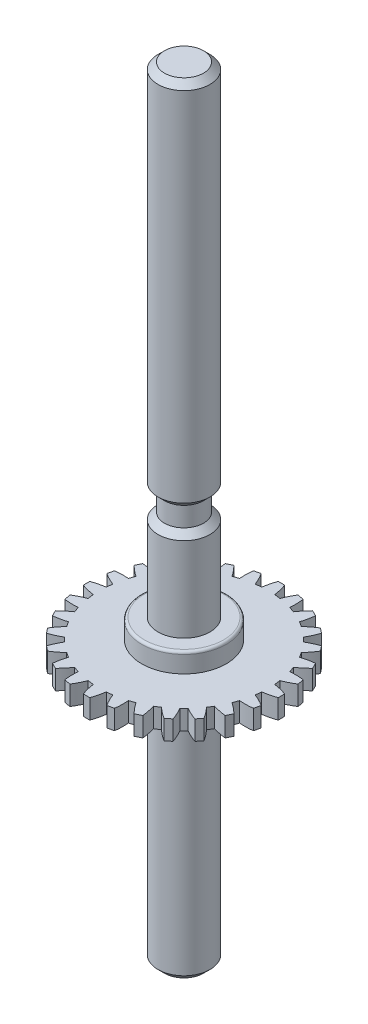
SolidWorks part; units mm, degrees
ref_plane "前视基准面" through (0, 0, 0) normal (0, 0, 1) x (1, 0, 0)
ref_plane "上视基准面" through (0, 0, 0) normal (0, 1, 0) x (1, 0, 0)
ref_plane "右视基准面" through (0, 0, 0) normal (1, 0, 0) x (0, 0, -1)
sketch "草图1" plane through (0, 0, 0) normal (0, 1, 0) x (1, 0, 0)
  circle A0 centre (0, 0) radius 6.5
extrude "凸台-拉伸1" add sketch "草图1" along normal blind 1.5
sketch "草图2" plane through (0, 1.5, 0) normal (0, 1, 0) x (-1, 0, 0)
  circle A0 centre (0, 0) radius 3.25
extrude "凸台-拉伸2" add sketch "草图2" along normal blind 1.5
sketch "草图3" plane through (0, 3, 0) normal (0, 1, 0) x (-1, 0, 0)
  circle A0 centre (0, 0) radius 2
extrude "凸台-拉伸3" add sketch "草图3" along normal blind 37
sketch "草图4" plane through (0, 1.5, 0) normal (0, 1, 0) x (-1, 0, 0)
  circle A0 centre (0, 0) radius 2
  circle A1 centre (0, 0) radius 1.5
extrude "切除-拉伸1" cut sketch "草图4" along normal blind 1.5 from offset 8.5
chamfer "倒角1" distance 0.5 angle 45 2 edges at (0, 10, 2) (0, 11.5, 2)
fillet "圆角1" radius 0.2 1 edges at (0, 3, 3.25)
sketch "草图9" plane through (0, 0, 0) normal (0, -1, 0) x (1, 0, 0)
  line L0 (1.4252, 7.3676) -> (1.9126, 7.2563)
  line L1 (-0.25, 7.5) -> (0.25, 7.5)
  line L2 (3.0289, 6.8657) -> (3.4794, 6.6488)
  line L3 (4.4807, 6.0196) -> (4.8716, 5.7079)
  line L4 (5.7079, 4.8716) -> (6.0196, 4.4807)
  line L5 (6.6488, 3.4794) -> (6.8657, 3.0289)
  line L6 (7.2563, 1.9126) -> (7.3676, 1.4252)
  line L7 (7.5, 0.25) -> (7.5, -0.25)
  line L8 (7.3676, -1.4252) -> (7.2563, -1.9126)
  line L9 (6.8657, -3.0289) -> (6.6488, -3.4794)
  line L10 (6.0196, -4.4807) -> (5.7079, -4.8716)
  line L11 (4.8716, -5.7079) -> (4.4807, -6.0196)
  line L12 (3.4794, -6.6488) -> (3.0289, -6.8657)
  line L13 (1.9126, -7.2563) -> (1.4252, -7.3676)
  line L14 (0.25, -7.5) -> (-0.25, -7.5)
  line L15 (-1.4252, -7.3676) -> (-1.9126, -7.2563)
  line L16 (-3.0289, -6.8657) -> (-3.4794, -6.6488)
  line L17 (-4.4807, -6.0196) -> (-4.8716, -5.7079)
  line L18 (-5.7079, -4.8716) -> (-6.0196, -4.4807)
  line L19 (-6.6488, -3.4794) -> (-6.8657, -3.0289)
  line L20 (-7.2563, -1.9126) -> (-7.3676, -1.4252)
  line L21 (-7.5, -0.25) -> (-7.5, 0.25)
  line L22 (-7.3676, 1.4252) -> (-7.2563, 1.9126)
  line L23 (-6.8657, 3.0289) -> (-6.6488, 3.4794)
  line L24 (-6.0196, 4.4807) -> (-5.7079, 4.8716)
  line L25 (-4.8716, 5.7079) -> (-4.4807, 6.0196)
  line L26 (-3.4794, 6.6488) -> (-3.0289, 6.8657)
  line L27 (-1.9126, 7.2563) -> (-1.4252, 7.3676)
  arc A0 (0.5, 6.4807) -> (-0.5, 6.4807) centre (0, 0) ccw
  arc A1 (0.5, 6.4807) -> (0.25, 7.5) centre (-4.6435, 5.7595) ccw
  arc A2 (-0.5, 6.4807) -> (-0.25, 7.5) centre (4.6435, 5.7595) cw
  arc A3 (1.9296, 6.207) -> (0.9546, 6.4295) centre (0, 0) ccw
  arc A4 (1.9296, 6.207) -> (1.9126, 7.2563) centre (-3.2454, 6.6483) ccw
  arc A5 (0.9546, 6.4295) -> (1.4252, 7.3676) centre (5.8086, 4.5818) cw
  arc A6 (3.2624, 5.622) -> (2.3614, 6.0559) centre (0, 0) ccw
  arc A7 (3.2624, 5.622) -> (3.4794, 6.6488) centre (-1.6847, 7.2038) ccw
  arc A8 (2.3614, 6.0559) -> (3.0289, 6.8657) centre (6.6826, 3.1744) cw
  arc A9 (4.4316, 4.7551) -> (3.6498, 5.3786) centre (0, 0) ccw
  arc A10 (4.4316, 4.7551) -> (4.8716, 5.7079) centre (-0.0394, 7.3981) ccw
  arc A11 (3.6498, 5.3786) -> (4.4807, 6.0196) centre (7.2214, 1.6078) cw
  arc A12 (5.3786, 3.6498) -> (4.7551, 4.4316) centre (0, 0) ccw
  arc A13 (5.3786, 3.6498) -> (6.0196, 4.4807) centre (1.6078, 7.2214) ccw
  arc A14 (4.7551, 4.4316) -> (5.7079, 4.8716) centre (7.3981, -0.0394) cw
  arc A15 (6.0559, 2.3614) -> (5.622, 3.2624) centre (0, 0) ccw
  arc A16 (6.0559, 2.3614) -> (6.8657, 3.0289) centre (3.1744, 6.6826) ccw
  arc A17 (5.622, 3.2624) -> (6.6488, 3.4794) centre (7.2038, -1.6847) cw
  arc A18 (6.4295, 0.9546) -> (6.207, 1.9296) centre (0, 0) ccw
  arc A19 (6.4295, 0.9546) -> (7.3676, 1.4252) centre (4.5818, 5.8086) ccw
  arc A20 (6.207, 1.9296) -> (7.2563, 1.9126) centre (6.6483, -3.2454) cw
  arc A21 (6.4807, -0.5) -> (6.4807, 0.5) centre (0, 0) ccw
  arc A22 (6.4807, -0.5) -> (7.5, -0.25) centre (5.7595, 4.6435) ccw
  arc A23 (6.4807, 0.5) -> (7.5, 0.25) centre (5.7595, -4.6435) cw
  arc A24 (6.207, -1.9296) -> (6.4295, -0.9546) centre (0, 0) ccw
  arc A25 (6.207, -1.9296) -> (7.2563, -1.9126) centre (6.6483, 3.2454) ccw
  arc A26 (6.4295, -0.9546) -> (7.3676, -1.4252) centre (4.5818, -5.8086) cw
  arc A27 (5.622, -3.2624) -> (6.0559, -2.3614) centre (0, 0) ccw
  arc A28 (5.622, -3.2624) -> (6.6488, -3.4794) centre (7.2038, 1.6847) ccw
  arc A29 (6.0559, -2.3614) -> (6.8657, -3.0289) centre (3.1744, -6.6826) cw
  arc A30 (4.7551, -4.4316) -> (5.3786, -3.6498) centre (0, 0) ccw
  arc A31 (4.7551, -4.4316) -> (5.7079, -4.8716) centre (7.3981, 0.0394) ccw
  arc A32 (5.3786, -3.6498) -> (6.0196, -4.4807) centre (1.6078, -7.2214) cw
  arc A33 (3.6498, -5.3786) -> (4.4316, -4.7551) centre (0, 0) ccw
  arc A34 (3.6498, -5.3786) -> (4.4807, -6.0196) centre (7.2214, -1.6078) ccw
  arc A35 (4.4316, -4.7551) -> (4.8716, -5.7079) centre (-0.0394, -7.3981) cw
  arc A36 (2.3614, -6.0559) -> (3.2624, -5.622) centre (0, 0) ccw
  arc A37 (2.3614, -6.0559) -> (3.0289, -6.8657) centre (6.6826, -3.1744) ccw
  arc A38 (3.2624, -5.622) -> (3.4794, -6.6488) centre (-1.6847, -7.2038) cw
  arc A39 (0.9546, -6.4295) -> (1.9296, -6.207) centre (0, 0) ccw
  arc A40 (0.9546, -6.4295) -> (1.4252, -7.3676) centre (5.8086, -4.5818) ccw
  arc A41 (1.9296, -6.207) -> (1.9126, -7.2563) centre (-3.2454, -6.6483) cw
  arc A42 (-0.5, -6.4807) -> (0.5, -6.4807) centre (0, 0) ccw
  arc A43 (-0.5, -6.4807) -> (-0.25, -7.5) centre (4.6435, -5.7595) ccw
  arc A44 (0.5, -6.4807) -> (0.25, -7.5) centre (-4.6435, -5.7595) cw
  arc A45 (-1.9296, -6.207) -> (-0.9546, -6.4295) centre (0, 0) ccw
  arc A46 (-1.9296, -6.207) -> (-1.9126, -7.2563) centre (3.2454, -6.6483) ccw
  arc A47 (-0.9546, -6.4295) -> (-1.4252, -7.3676) centre (-5.8086, -4.5818) cw
  arc A48 (-3.2624, -5.622) -> (-2.3614, -6.0559) centre (0, 0) ccw
  arc A49 (-3.2624, -5.622) -> (-3.4794, -6.6488) centre (1.6847, -7.2038) ccw
  arc A50 (-2.3614, -6.0559) -> (-3.0289, -6.8657) centre (-6.6826, -3.1744) cw
  arc A51 (-4.4316, -4.7551) -> (-3.6498, -5.3786) centre (0, 0) ccw
  arc A52 (-4.4316, -4.7551) -> (-4.8716, -5.7079) centre (0.0394, -7.3981) ccw
  arc A53 (-3.6498, -5.3786) -> (-4.4807, -6.0196) centre (-7.2214, -1.6078) cw
  arc A54 (-5.3786, -3.6498) -> (-4.7551, -4.4316) centre (0, 0) ccw
  arc A55 (-5.3786, -3.6498) -> (-6.0196, -4.4807) centre (-1.6078, -7.2214) ccw
  arc A56 (-4.7551, -4.4316) -> (-5.7079, -4.8716) centre (-7.3981, 0.0394) cw
  arc A57 (-6.0559, -2.3614) -> (-5.622, -3.2624) centre (0, 0) ccw
  arc A58 (-6.0559, -2.3614) -> (-6.8657, -3.0289) centre (-3.1744, -6.6826) ccw
  arc A59 (-5.622, -3.2624) -> (-6.6488, -3.4794) centre (-7.2038, 1.6847) cw
  arc A60 (-6.4295, -0.9546) -> (-6.207, -1.9296) centre (0, 0) ccw
  arc A61 (-6.4295, -0.9546) -> (-7.3676, -1.4252) centre (-4.5818, -5.8086) ccw
  arc A62 (-6.207, -1.9296) -> (-7.2563, -1.9126) centre (-6.6483, 3.2454) cw
  arc A63 (-6.4807, 0.5) -> (-6.4807, -0.5) centre (0, 0) ccw
  arc A64 (-6.4807, 0.5) -> (-7.5, 0.25) centre (-5.7595, -4.6435) ccw
  arc A65 (-6.4807, -0.5) -> (-7.5, -0.25) centre (-5.7595, 4.6435) cw
  arc A66 (-6.207, 1.9296) -> (-6.4295, 0.9546) centre (0, 0) ccw
  arc A67 (-6.207, 1.9296) -> (-7.2563, 1.9126) centre (-6.6483, -3.2454) ccw
  arc A68 (-6.4295, 0.9546) -> (-7.3676, 1.4252) centre (-4.5818, 5.8086) cw
  arc A69 (-5.622, 3.2624) -> (-6.0559, 2.3614) centre (0, 0) ccw
  arc A70 (-5.622, 3.2624) -> (-6.6488, 3.4794) centre (-7.2038, -1.6847) ccw
  arc A71 (-6.0559, 2.3614) -> (-6.8657, 3.0289) centre (-3.1744, 6.6826) cw
  arc A72 (-4.7551, 4.4316) -> (-5.3786, 3.6498) centre (0, 0) ccw
  arc A73 (-4.7551, 4.4316) -> (-5.7079, 4.8716) centre (-7.3981, -0.0394) ccw
  arc A74 (-5.3786, 3.6498) -> (-6.0196, 4.4807) centre (-1.6078, 7.2214) cw
  arc A75 (-3.6498, 5.3786) -> (-4.4316, 4.7551) centre (0, 0) ccw
  arc A76 (-3.6498, 5.3786) -> (-4.4807, 6.0196) centre (-7.2214, 1.6078) ccw
  arc A77 (-4.4316, 4.7551) -> (-4.8716, 5.7079) centre (0.0394, 7.3981) cw
  arc A78 (-2.3614, 6.0559) -> (-3.2624, 5.622) centre (0, 0) ccw
  arc A79 (-2.3614, 6.0559) -> (-3.0289, 6.8657) centre (-6.6826, 3.1744) ccw
  arc A80 (-3.2624, 5.622) -> (-3.4794, 6.6488) centre (1.6847, 7.2038) cw
  arc A81 (-0.9546, 6.4295) -> (-1.9296, 6.207) centre (0, 0) ccw
  arc A82 (-0.9546, 6.4295) -> (-1.4252, 7.3676) centre (-5.8086, 4.5818) ccw
  arc A83 (-1.9296, 6.207) -> (-1.9126, 7.2563) centre (3.2454, 6.6483) cw
  point P5 (0, 7.5)
  point P13 (1.6689, 7.312)
  point P21 (3.2541, 6.7573)
  point P29 (4.6762, 5.8637)
  point P37 (5.8637, 4.6762)
  point P45 (6.7573, 3.2541)
  point P53 (7.312, 1.6689)
  point P61 (7.5, 0)
  point P69 (7.312, -1.6689)
  point P77 (6.7573, -3.2541)
  point P85 (5.8637, -4.6762)
  point P93 (4.6762, -5.8637)
  point P101 (3.2541, -6.7573)
  point P109 (1.6689, -7.312)
  point P117 (0, -7.5)
  point P125 (-1.6689, -7.312)
  point P133 (-3.2541, -6.7573)
  point P141 (-4.6762, -5.8637)
  point P149 (-5.8637, -4.6762)
  point P157 (-6.7573, -3.2541)
  point P165 (-7.312, -1.6689)
  point P173 (-7.5, 0)
  point P181 (-7.312, 1.6689)
  point P189 (-6.7573, 3.2541)
  point P197 (-5.8637, 4.6762)
  point P205 (-4.6762, 5.8637)
  point P213 (-3.2541, 6.7573)
  point P221 (-1.6689, 7.312)
  dimension "D1" = 28
extrude "凸台-拉伸4" add sketch "草图9" against normal up to surface (1.5 mm away) up to face at (0, 1.5, 6.5)
sketch "草图10" plane through (0, 0, 0) normal (0, -1, 0) x (1, 0, 0)
  circle A0 centre (0, 0) radius 2
  dimension "D1" = 4
extrude "凸台-拉伸5" add sketch "草图10" along normal blind 20
chamfer "倒角2" distance 0.5 angle 45 2 edges at (0, 40, 2) (0, -20, -2)
